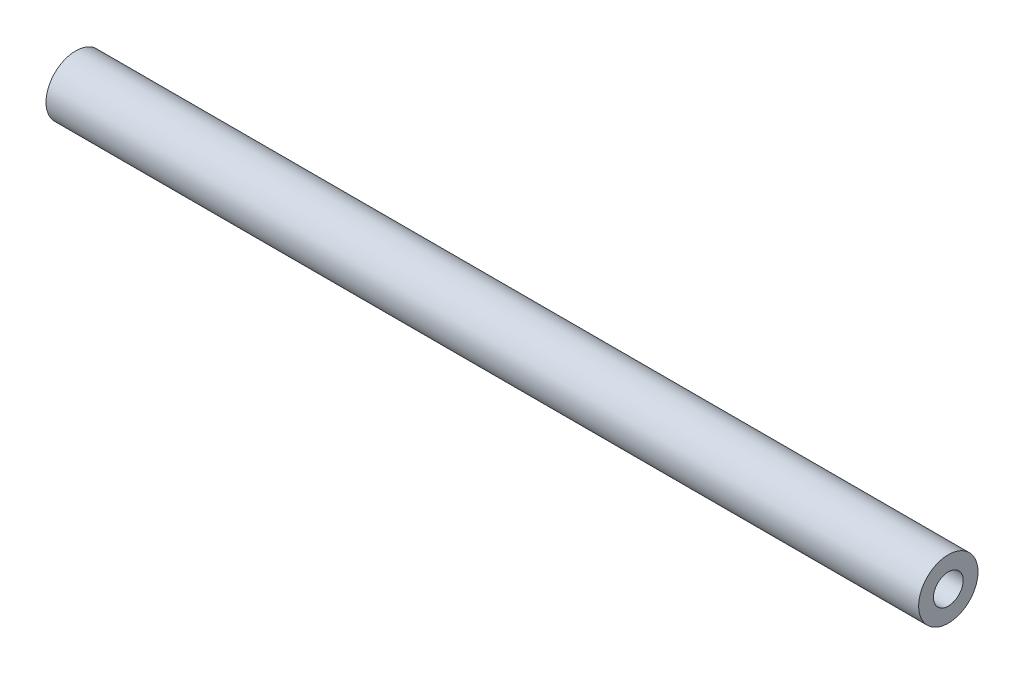
SolidWorks part; units mm, degrees
material "AISI 4130 Steel, normalized at 870C"
ref_plane "Front Plane" through (0, 0, 0) normal (0, 0, 1) x (1, 0, 0)
ref_plane "Top Plane" through (0, 0, 0) normal (0, 1, 0) x (1, 0, 0)
ref_plane "Right Plane" through (0, 0, 0) normal (1, 0, 0) x (0, 0, -1)
sketch "Sketch1" plane through (0, 0, 0) normal (1, 0, 0) x (0, 0, -1)
  circle A0 centre (0, 0) radius 10
extrude "Boss-Extrude1" add sketch "Sketch1" along normal blind 127 and the other way blind 127
sketch "Sketch2" plane through (127, 0, 0) normal (1, 0, 0) x (0, 0, -1)
  circle A0 centre (0, 0) radius 5
  circle A1 centre (0, 0) radius 10
extrude "Boss-Extrude2" add sketch "Sketch2" along normal blind 20
sketch "Sketch3" plane through (-127, 0, 0) normal (-1, 0, 0) x (0, 0, 1)
  circle A0 centre (0, 0) radius 5
  circle A1 centre (0, 0) radius 10
extrude "Boss-Extrude3" add sketch "Sketch3" along normal blind 20
